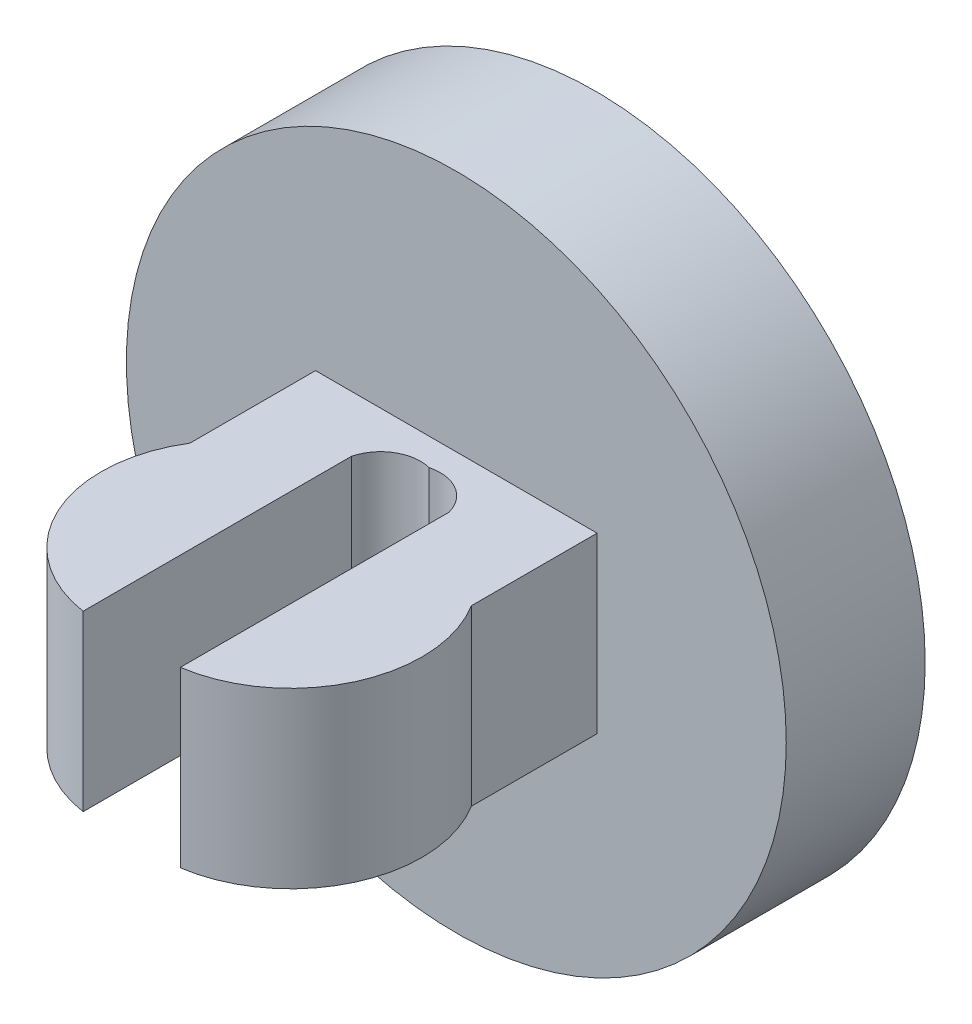
SolidWorks part; units mm, degrees
ref_plane "Front Plane" through (0, 0, 0) normal (0, 0, 1) x (1, 0, 0)
ref_plane "Top Plane" through (0, 0, 0) normal (0, 1, 0) x (1, 0, 0)
ref_plane "Right Plane" through (0, 0, 0) normal (1, 0, 0) x (0, 0, -1)
sketch "Sketch1" plane through (0, 0, 0) normal (0, 0, 1) x (1, 0, 0)
  circle A0 centre (0, 0) radius 9.5
  dimension "D1" = 19
extrude "Boss-Extrude1" add sketch "Sketch1" along normal blind 4
sketch "Sketch3" plane through (0, 0, 0) normal (0, 1, 0) x (1, 0, 0)
  line L0 (-9.5, -4) -> (9.5, -4) construction
  line L1 (0, 0) -> (0, -14.3724) construction
  line L3 (-4.053, -4) -> (4.053, -4)
  line L6 (-1.4, -5.6188) -> (-1.4, -13.3459)
  line L7 (-4.5469, -7.7337) -> (-4.5469, -11.8821) construction
  line L8 (-4.053, -7.6166) -> (-4.053, -4)
  line L9 (4.053, -7.6166) -> (4.053, -4)
  line L10 (1.4, -5.6188) -> (1.4, -13.3459)
  arc A1 (-4.053, -7.6166) -> (-1.4, -13.3459) centre (-0.8382, -9.6068) ccw
  arc A7 (4.053, -7.6166) -> (1.4, -13.3459) centre (0.8382, -9.6068) cw
  arc A8 (-1.4, -5.6188) -> (0, -4.7829) centre (-0.2821, -5.9008) cw
  arc A9 (1.4, -5.6188) -> (0, -4.7829) centre (0.2821, -5.9008) ccw
  point P21 (0, -4)
  dimension "D1" = 0.4939
  dimension "D2" = 1.4
  dimension "D3" = 4.5469
extrude "Boss-Extrude2" add sketch "Sketch3" along normal mid plane 5
